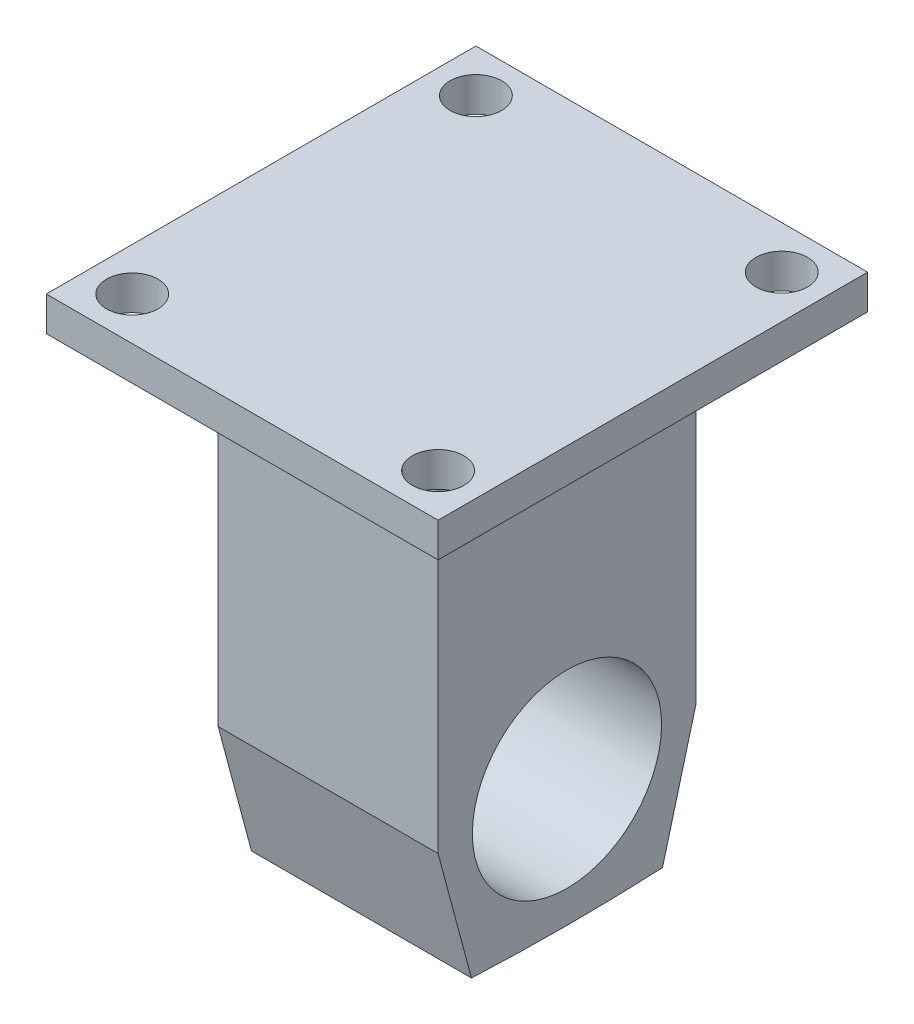
SolidWorks part; units mm, degrees
material "ABS"
ref_plane "Front Plane" through (0, 0, 0) normal (0, 0, 1) x (1, 0, 0)
ref_plane "Top Plane" through (0, 0, 0) normal (0, 1, 0) x (1, 0, 0)
ref_plane "Right Plane" through (0, 0, 0) normal (1, 0, 0) x (0, 0, -1)
sketch "Sketch1" plane through (0, 0, 0) normal (0, 1, 0) x (1, 0, 0)
  line L1 (-16.256, -19.05) -> (16.256, -19.05)
  line L2 (-16.256, -19.05) -> (-16.256, 19.05)
  line L3 (-16.256, 19.05) -> (16.256, 19.05)
  line L4 (16.256, -19.05) -> (16.256, 19.05)
  line L5 (-16.256, -19.05) -> (16.256, 19.05) construction
  line L6 (-16.256, 19.05) -> (16.256, -19.05) construction
  point P0 (0, 0)
extrude "Boss-Extrude1" add sketch "Sketch1" along normal blind 50.292
sketch "Sketch2" plane through (16.256, 0, 0) normal (1, 0, 0) x (0, 0, -1)
  line L0 (-19.05, 0) -> (-14.1195, -18.4009)
  line L1 (19.05, 0) -> (14.1195, -18.4009)
  line L2 (-19.05, 0) -> (19.05, 0)
  line L3 (-19.05, 0) -> (19.05, 0) construction
  arc A1 (14.1195, -18.4009) -> (-14.1195, -18.4009) centre (0, 281.2546) cw
  dimension "D1" = 19.05
  dimension "D2" = 19.05
  dimension "D3" = 75
  dimension "D4" = 75
extrude "Boss-Extrude2" add sketch "Sketch2" against normal up to vertex (32.512 mm away) contours L0 A1 L1 L2 up to point (-16.256, 0, -19.05)
sketch "Sketch3" plane through (16.256, 0, 0) normal (1, 0, 0) x (0, 0, -1)
  circle A0 centre (0, 0) radius 13.9872
extrude "Cut-Extrude1" cut sketch "Sketch3" against normal blind 127 contours A0
sketch "Sketch4" plane through (0, 50.292, 0) normal (0, 1, 0) x (1, 0, 0)
  line L1 (28.956, -31.75) -> (-28.956, -31.75)
  line L2 (28.956, -31.75) -> (28.956, 31.75)
  line L3 (28.956, 31.75) -> (-28.956, 31.75)
  line L4 (-28.956, -31.75) -> (-28.956, 31.75)
  line L5 (28.956, -31.75) -> (-28.956, 31.75) construction
  line L6 (28.956, 31.75) -> (-28.956, -31.75) construction
  point P0 (0, 0)
extrude "Boss-Extrude3" add sketch "Sketch4" along normal blind 5.08
sketch "Sketch5" plane through (0, 55.372, 0) normal (0, 1, 0) x (1, 0, 0)
  line L0 (0, -31.75) -> (0, 31.75) construction
  line L1 (28.956, 31.75) -> (-28.956, 31.75) construction
  line L2 (-28.956, 0) -> (28.956, 0) construction
  line L3 (28.956, -31.75) -> (28.956, 31.75) construction
  line L4 (-22.606, -31.75) -> (-22.606, 31.75) construction
  line L5 (-28.956, 25.4) -> (28.956, 25.4) construction
  line L6 (-28.956, 31.75) -> (-28.956, -31.75) construction
  circle A0 centre (-22.606, 25.4) radius 3.81
  circle A1 centre (-22.606, -25.4) radius 3.81
  circle A2 centre (22.606, 25.4) radius 3.81
  circle A3 centre (22.606, -25.4) radius 3.81
  point P6 (0, 0)
  point P12 (0, 0)
  point P15 (-22.606, 0)
  point P18 (0, 25.4)
  point P20 (-22.606, 25.4)
  dimension "D1" = 6.35
  dimension "D2" = 6.35
  dimension "D3" = 0
extrude "Cut-Extrude2" cut sketch "Sketch5" against normal blind 5.08
